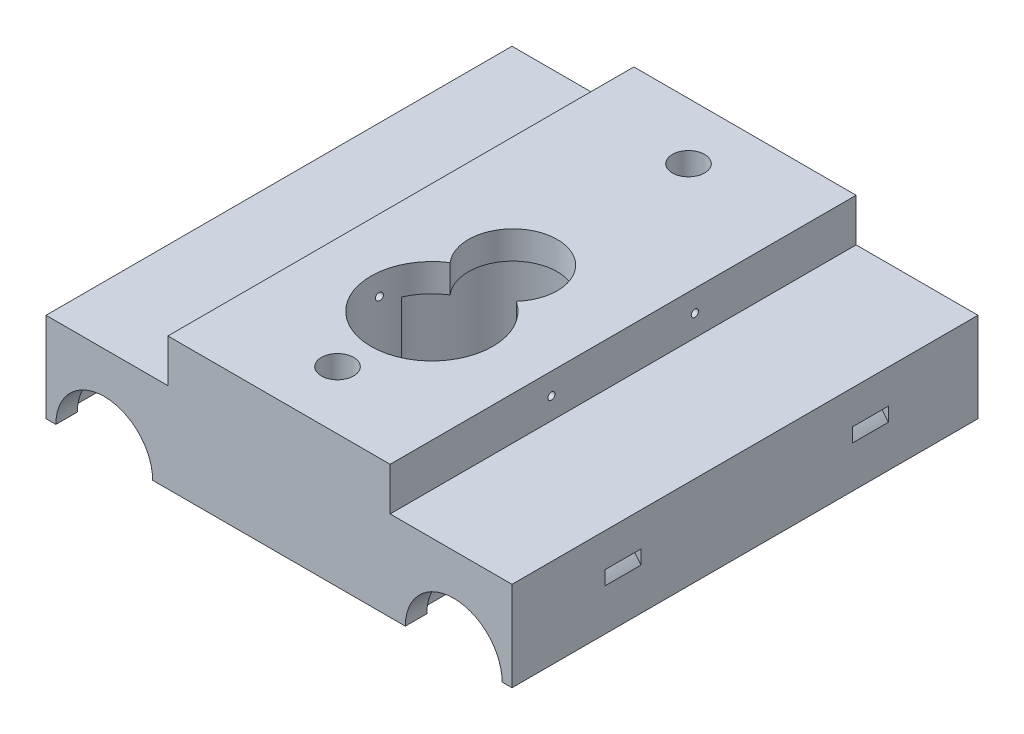
SolidWorks part; units mm, degrees
ref_plane "Спереди" through (0, 0, 0) normal (0, 0, 1) x (1, 0, 0)
ref_plane "Сверху" through (0, 0, 0) normal (0, 1, 0) x (1, 0, 0)
ref_plane "Справа" through (0, 0, 0) normal (1, 0, 0) x (0, 0, -1)
sketch "Эскиз1" plane through (0, 0, 0) normal (0, 1, 0) x (1, 0, 0)
  line L1 (-24.8662, 24.0482) -> (40.1338, 24.0482)
  line L2 (-24.8662, 24.0482) -> (-24.8662, -40.9518)
  line L3 (-24.8662, -40.9518) -> (40.1338, -40.9518)
  line L4 (40.1338, 24.0482) -> (40.1338, -40.9518)
  dimension "D1" = 65
extrude "Бобышка-Вытянуть1" add sketch "Эскиз1" along normal blind 17
ref_plane "Плоскость1" through (0, 0, 37.9518) normal (0, 0, 1) x (1, 0, 0)
sketch "Эскиз3" plane through (0, 0, 37.9518) normal (0, 0, 1) x (1, 0, 0)
  line L0 (7.6338, 20.5799) -> (-16.7362, 20.5799) construction
  line L1 (7.6338, 20.5799) -> (32.0038, 20.5799) construction
  line L2 (39.7538, 8.5) -> (40.1338, 8.5)
  line L3 (40.1338, 17) -> (40.1338, 0) construction
  line L4 (40.1338, 8.5) -> (40.1338, 0)
  line L5 (40.1338, 0) -> (24.2538, 0)
  line L6 (-24.8662, 0) -> (40.1338, 0) construction
  line L7 (24.2538, 0) -> (24.2538, 8.5)
  line L8 (-24.4862, 8.5) -> (-24.8662, 8.5)
  line L9 (-24.8662, 17) -> (-24.8662, 0) construction
  line L10 (-24.8662, 8.5) -> (-24.8662, 0)
  line L11 (-24.8662, 0) -> (-8.9862, 0)
  line L12 (-8.9862, 0) -> (-8.9862, 8.5)
  arc A0 (-8.9862, 8.5) -> (-24.4862, 8.5) centre (-16.7362, 8.5) ccw
  arc A1 (39.7538, 8.5) -> (24.2538, 8.5) centre (32.0038, 8.5) ccw
  dimension "D3" = 15.5
  dimension "D4" = 15.5
  dimension "D1" = 24.37
  dimension "D2" = 24.37
extrude "Вырез-Вытянуть1" cut sketch "Эскиз3" against normal blind 59
ref_plane "Плоскость3" through (0, 0, 13.4518) normal (0, 0, 1) x (1, 0, 0)
sketch "Эскиз5" plane through (0, 0, 40.9518) normal (0, 0, 1) x (1, 0, 0)
  line L0 (7.6338, 22.8915) -> (-16.7362, 22.8915) construction
  line L1 (7.6338, 22.8915) -> (32.0038, 22.8915) construction
  line L2 (-23.4862, 8.5) -> (-24.8662, 8.5)
  line L3 (-24.8662, 17) -> (-24.8662, 0) construction
  line L4 (-24.8662, 8.5) -> (-24.8662, 0)
  line L5 (-24.8662, 0) -> (-9.9862, 0)
  line L6 (-24.8662, 0) -> (40.1338, 0) construction
  line L7 (-9.9862, 0) -> (-9.9862, 8.5)
  line L8 (38.7538, 8.5) -> (40.1338, 8.5)
  line L9 (40.1338, 17) -> (40.1338, 0) construction
  line L10 (40.1338, 8.5) -> (40.1338, 0)
  line L11 (40.1338, 0) -> (25.2538, 0)
  line L12 (25.2538, 0) -> (25.2538, 8.5)
  arc A0 (-9.9862, 8.5) -> (-23.4862, 8.5) centre (-16.7362, 8.5) ccw
  arc A1 (38.7538, 8.5) -> (25.2538, 8.5) centre (32.0038, 8.5) ccw
  dimension "D3" = 13.5
  dimension "D4" = 13.5
  dimension "D1" = 24.37
  dimension "D2" = 24.37
extrude "Вырез-Вытянуть2" cut sketch "Эскиз5" against normal through all
sketch "Эскиз6" plane through (0, 0, 13.4518) normal (0, 0, 1) x (1, 0, 0)
  line L0 (-23.4862, 8.5) -> (-24.8662, 8.5)
  line L1 (-24.8662, 8.5) -> (-24.8662, 17)
  line L2 (-24.8662, 17) -> (-9.9862, 17)
  line L3 (-24.8662, 17) -> (40.1338, 17) construction
  line L4 (40.1338, 17) -> (40.1338, 8.5)
  line L5 (40.1338, 17) -> (40.1338, 8.5) construction
  line L6 (40.1338, 8.5) -> (38.7538, 8.5)
  line L7 (-9.9862, 8.5) -> (-9.9862, 0)
  line L8 (-9.9862, 0) -> (25.2538, 0)
  line L9 (25.2538, 0) -> (25.2538, 8.5)
  line L10 (-9.9862, 17) -> (40.1338, 17)
  arc A0 (-9.9862, 8.5) -> (-23.4862, 8.5) centre (-16.7362, 8.5) ccw
  arc A1 (38.7538, 8.5) -> (25.2538, 8.5) centre (32.0038, 8.5) ccw
extrude "Бобышка-Вытянуть2" add sketch "Эскиз6" against normal blind 10 contours L7 L8 L9 A1 L6 L4 L10 L2 L1 L0 A0
sketch "Эскиз12" plane through (0, 0, 40.9518) normal (0, 0, 1) x (1, 0, 0)
  line L0 (-9.9862, 8.5) -> (-9.9862, 0)
  line L1 (-9.9862, 0) -> (25.2538, 0)
  line L3 (25.2538, 0) -> (25.2538, 8.5)
  line L5 (25.2538, 8.5) -> (-9.9862, 8.5)
extrude "Вырез-Вытянуть5" cut sketch "Эскиз12" against normal through all
sketch "Эскиз17" plane through (0, 17, 0) normal (0, 1, 0) x (1, 0, 0)
  line L0 (-29.2175, -8.3313) -> (-29.2175, 16.1687) construction
  line L1 (-29.2175, -8.3313) -> (-29.2175, -32.8313) construction
  line L2 (7.6338, 34.0476) -> (7.6338, -69.5456) construction
  circle A0 centre (7.6338, 16.1687) radius 2.25
  circle A1 centre (7.6762, -32.8313) radius 2.25
  dimension "D3" = 4.5
  dimension "D4" = 4.5
  dimension "D1" = 24.5
  dimension "D2" = 24.5
extrude "Вырез-Вытянуть8" cut sketch "Эскиз17" against normal through all
sketch "Эскиз18" plane through (0, 17, 0) normal (0, 1, 0) x (1, 0, 0)
  line L1 (-24.8662, 24.0482) -> (40.1338, 24.0482)
  line L2 (-24.8662, 24.0482) -> (-24.8662, -40.9518)
  line L3 (-24.8662, -40.9518) -> (40.1338, -40.9518)
  line L4 (40.1338, 24.0482) -> (40.1338, -40.9518)
  circle A2 centre (7.6338, 16.1687) radius 2.25
  circle A3 centre (7.6762, -32.8313) radius 2.25
extrude "Бобышка-Вытянуть3" add sketch "Эскиз18" along normal blind 10
sketch "Эскиз9" plane through (0, 0, 37.9518) normal (0, 0, 1) x (1, 0, 0)
  circle A0 centre (-16.7362, 8.5) radius 10
  circle A1 centre (-16.7362, 8.5) radius 11.25
  circle A2 centre (32.0038, 8.5) radius 11.25
  circle A3 centre (32.0038, 8.5) radius 10
  dimension "D1" = 20
  dimension "D2" = 22.5
  dimension "D3" = 22.5
  dimension "D4" = 20
extrude "Вырез-Вытянуть3" cut sketch "Эскиз9" against normal blind 5 from offset 10 offset against normal yes
sketch "Эскиз10" plane through (0, 0, 13.4518) normal (0, 0, 1) x (1, 0, 0)
  circle A0 centre (-16.7362, 8.5) radius 11.25
  circle A1 centre (32.0038, 8.5) radius 11.25
  circle A2 centre (-16.7362, 8.5) radius 10
  circle A3 centre (32.0038, 8.5) radius 10
  dimension "D1" = 22.5
  dimension "D2" = 22.5
  dimension "D3" = 20
  dimension "D4" = 20
extrude "Вырез-Вытянуть4" cut sketch "Эскиз10" against normal blind 5 from offset 20 offset against normal yes
sketch "Эскиз19" plane through (40.1338, 0, 0) normal (1, 0, 0) x (0, 0, -1)
  line L0 (24.0482, 27) -> (24.0482, 8.5) construction
  line L1 (-40.9518, 27) -> (24.0482, 27)
  line L2 (-40.9518, 27) -> (-40.9518, 21)
  line L3 (-40.9518, 21) -> (24.0482, 21)
  line L4 (24.0482, 27) -> (24.0482, 21)
  dimension "D1" = 6
extrude "Вырез-Вытянуть9" cut sketch "Эскиз19" against normal blind 17
sketch "Эскиз20" plane through (-24.8662, 0, 0) normal (-1, 0, 0) x (0, 0, 1)
  line L1 (-24.0482, 27) -> (40.9518, 27)
  line L2 (-24.0482, 27) -> (-24.0482, 21)
  line L3 (-24.0482, 21) -> (40.9518, 21)
  line L4 (40.9518, 27) -> (40.9518, 21)
  line L5 (40.9518, 27) -> (40.9518, 8.5) construction
  dimension "D1" = 6
  dimension "D2" = 65
extrude "Вырез-Вытянуть10" cut sketch "Эскиз20" against normal blind 17
sketch "Эскиз21" plane through (23.1338, 0, 0) normal (1, 0, 0) x (0, 0, -1)
  line L0 (-8.4518, 31.4091) -> (-18.4518, 31.4091) construction
  line L1 (-18.4518, 31.4091) -> (1.5482, 31.4091) construction
  circle A0 centre (-18.4518, 24) radius 0.5
  circle A1 centre (1.5482, 24) radius 0.5
  dimension "D3" = 1
  dimension "D4" = 1
  dimension "D1" = 10
  dimension "D2" = 20
extrude "Вырез-Вытянуть11" cut sketch "Эскиз21" against normal through all
sketch "Эскиз22" plane through (0, 21, 0) normal (0, 1, 0) x (1, 0, 0)
  line L0 (-28.9005, 22.5482) -> (-28.9005, 17.5482) construction
  line L1 (-7.8662, 24.0482) -> (-7.8662, -40.9518) construction
  line L2 (-24.8662, 24.0482) -> (-7.8662, 24.0482)
  line L3 (-24.8662, 24.0482) -> (-24.8662, 22.5482)
  line L4 (-24.8662, 22.5482) -> (-7.8662, 22.5482)
  line L5 (-7.8662, 24.0482) -> (-7.8662, 22.5482)
  line L6 (-24.8662, 24.0482) -> (-24.8662, -40.9518) construction
  line L7 (-24.8662, 17.5482) -> (-7.8662, 17.5482)
  line L8 (-24.8662, 17.5482) -> (-24.8662, 16.0482)
  line L9 (-24.8662, 16.0482) -> (-7.8662, 16.0482)
  line L10 (-7.8662, 17.5482) -> (-7.8662, 16.0482)
  line L11 (-7.8662, -40.9518) -> (-7.8662, 24.0482) construction
  line L12 (-24.8662, 11.5482) -> (-7.8662, 11.5482)
  line L13 (-24.8662, 11.5482) -> (-24.8662, 10.0482)
  line L14 (-24.8662, 10.0482) -> (-7.8662, 10.0482)
  line L15 (-7.8662, 11.5482) -> (-7.8662, 10.0482)
  line L16 (-24.8662, 5.0482) -> (-7.8662, 5.0482)
  line L17 (-24.8662, 5.0482) -> (-24.8662, 3.5482)
  line L18 (-24.8662, 3.5482) -> (-7.8662, 3.5482)
  line L19 (-7.8662, 5.0482) -> (-7.8662, 3.5482)
  line L20 (-24.8662, -0.9518) -> (-7.8662, -0.9518)
  line L21 (-24.8662, -0.9518) -> (-24.8662, -2.4518)
  line L22 (-24.8662, -2.4518) -> (-7.8662, -2.4518)
  line L23 (-7.8662, -0.9518) -> (-7.8662, -2.4518)
  line L24 (-24.8662, -7.4518) -> (-7.8662, -7.4518)
  line L25 (-24.8662, -7.4518) -> (-24.8662, -8.9518)
  line L26 (-24.8662, -8.9518) -> (-7.8662, -8.9518)
  line L27 (-7.8662, -7.4518) -> (-7.8662, -8.9518)
  line L28 (-24.8662, -13.4518) -> (-7.8662, -13.4518)
  line L29 (-24.8662, -13.4518) -> (-24.8662, -14.9518)
  line L30 (-24.8662, -14.9518) -> (-7.8662, -14.9518)
  line L31 (-7.8662, -13.4518) -> (-7.8662, -14.9518)
  line L32 (-24.8662, -19.9518) -> (-7.8662, -19.9518)
  line L33 (-24.8662, -19.9518) -> (-24.8662, -21.4518)
  line L34 (-24.8662, -21.4518) -> (-7.8662, -21.4518)
  line L35 (-7.8662, -19.9518) -> (-7.8662, -21.4518)
  line L36 (-24.8662, -25.9518) -> (-7.8662, -25.9518)
  line L37 (-24.8662, -25.9518) -> (-24.8662, -27.4518)
  line L38 (-24.8662, -27.4518) -> (-7.8662, -27.4518)
  line L39 (-7.8662, -25.9518) -> (-7.8662, -27.4518)
  line L40 (-24.8662, -32.4518) -> (-7.8662, -32.4518)
  line L41 (-24.8662, -32.4518) -> (-24.8662, -33.9518)
  line L42 (-24.8662, -33.9518) -> (-7.8662, -33.9518)
  line L43 (-7.8662, -32.4518) -> (-7.8662, -33.9518)
  line L44 (-24.8662, -39.4518) -> (-7.8662, -39.4518)
  line L45 (-24.8662, -39.4518) -> (-24.8662, -40.9518)
  line L46 (-24.8662, -40.9518) -> (-7.8662, -40.9518)
  line L47 (-7.8662, -39.4518) -> (-7.8662, -40.9518)
  line L48 (23.1338, 24.0482) -> (40.1338, 24.0482)
  line L49 (23.1338, 24.0482) -> (23.1338, 22.5482)
  line L50 (23.1338, 22.5482) -> (40.1338, 22.5482)
  line L51 (40.1338, 24.0482) -> (40.1338, 22.5482)
  line L52 (23.1338, 17.5482) -> (40.1338, 17.5482)
  line L53 (23.1338, 17.5482) -> (23.1338, 16.0482)
  line L54 (23.1338, 16.0482) -> (40.1338, 16.0482)
  line L55 (40.1338, 17.5482) -> (40.1338, 16.0482)
  line L56 (23.1338, 11.5482) -> (40.1338, 11.5482)
  line L57 (23.1338, 11.5482) -> (23.1338, 10.0482)
  line L58 (23.1338, 10.0482) -> (40.1338, 10.0482)
  line L59 (40.1338, 11.5482) -> (40.1338, 10.0482)
  line L60 (23.1338, 5.0482) -> (40.1338, 5.0482)
  line L61 (23.1338, 5.0482) -> (23.1338, 3.5482)
  line L62 (23.1338, 3.5482) -> (40.1338, 3.5482)
  line L63 (40.1338, 5.0482) -> (40.1338, 3.5482)
  line L64 (23.1338, -0.9518) -> (40.1338, -0.9518)
  line L65 (23.1338, -0.9518) -> (23.1338, -2.4518)
  line L66 (23.1338, -2.4518) -> (40.1338, -2.4518)
  line L67 (40.1338, -0.9518) -> (40.1338, -2.4518)
  line L68 (23.1338, -7.4518) -> (40.1338, -7.4518)
  line L69 (23.1338, -7.4518) -> (23.1338, -8.9518)
  line L70 (23.1338, -8.9518) -> (40.1338, -8.9518)
  line L71 (40.1338, -7.4518) -> (40.1338, -8.9518)
  line L72 (23.1338, -13.4518) -> (40.1338, -13.4518)
  line L73 (23.1338, -13.4518) -> (23.1338, -14.9518)
  line L74 (23.1338, -14.9518) -> (40.1338, -14.9518)
  line L75 (40.1338, -13.4518) -> (40.1338, -14.9518)
  line L76 (23.1338, -19.9518) -> (40.1338, -19.9518)
  line L77 (23.1338, -19.9518) -> (23.1338, -21.4518)
  line L78 (23.1338, -21.4518) -> (40.1338, -21.4518)
  line L79 (40.1338, -19.9518) -> (40.1338, -21.4518)
  line L80 (23.1338, -25.9518) -> (40.1338, -25.9518)
  line L81 (23.1338, -25.9518) -> (23.1338, -27.4518)
  line L82 (23.1338, -27.4518) -> (40.1338, -27.4518)
  line L83 (40.1338, -25.9518) -> (40.1338, -27.4518)
  line L84 (23.1338, -32.4518) -> (40.1338, -32.4518)
  line L85 (23.1338, -32.4518) -> (23.1338, -33.9518)
  line L86 (23.1338, -33.9518) -> (40.1338, -33.9518)
  line L87 (40.1338, -32.4518) -> (40.1338, -33.9518)
  line L88 (23.1338, -39.4518) -> (40.1338, -39.4518)
  line L89 (23.1338, -39.4518) -> (23.1338, -40.9518)
  line L90 (23.1338, -40.9518) -> (40.1338, -40.9518)
  line L91 (40.1338, -39.4518) -> (40.1338, -40.9518)
  line L92 (19.0995, 22.5482) -> (19.0995, 17.5482) construction
  line L93 (-24.8662, 24.0482) -> (23.1338, 24.0482) construction
  dimension "D1" = 5
  dimension "D2" = 1.5
  dimension "D3" = 1.5
  dimension "D4" = 2
  dimension "D5" = 48
extrude "Бобышка-Вытянуть4" [suppressed] add sketch "Эскиз22" along normal up to surface (6 mm away) up to face at (7.6338, 27, -13.9187)
sketch "Эскиз13" plane through (0, 27, 0) normal (0, -1, 0) x (1, 0, 0)
  arc A0 (2.9621, 12.4074) -> (12.2503, 12.4699) centre (7.6338, 8.3313) ccw
  arc A3 (12.2503, 12.4699) -> (2.9621, 12.4074) centre (7.5583, 19.5576) ccw
  dimension "D1" = 12.4
extrude "Вырез-Вытянуть12" cut sketch "Эскиз13" along normal blind 3.9 contours A0 A3
sketch "Эскиз24" plane through (0, 23.1, 0) normal (0, 1, 0) x (1, 0, 0)
  arc A1 (-0.1902, -16.0633) -> (15.3532, -16.1678) centre (7.5583, -19.5576) ccw
  arc A2 (15.3532, -16.1678) -> (-0.1902, -16.0633) centre (7.6338, -8.3313) ccw
  dimension "D2" = 22
extrude "Вырез-Вытянуть13" cut sketch "Эскиз24" against normal through all
